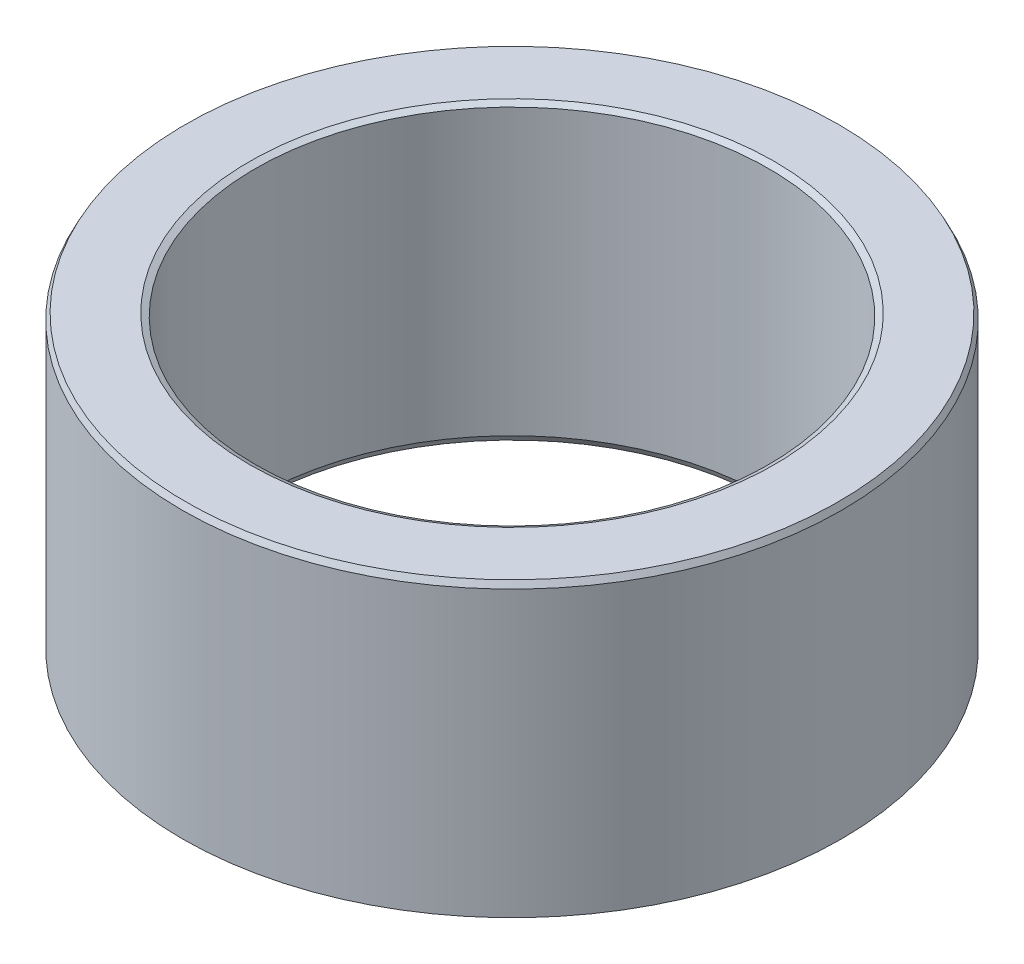
SolidWorks part; units mm, degrees
ref_plane "Front Plane" through (0, 0, 0) normal (0, 0, 1) x (1, 0, 0)
ref_plane "Top Plane" through (0, 0, 0) normal (0, 1, 0) x (1, 0, 0)
ref_plane "Right Plane" through (0, 0, 0) normal (1, 0, 0) x (0, 0, -1)
sketch "Sketch1" plane through (0, 0, 0) normal (0, 1, 0) x (1, 0, 0)
  circle A0 centre (0, 0) radius 30
  dimension "SLEEVE_OD" = 60
extrude "Boss-Extrude1" add sketch "Sketch1" along normal blind 26.7156
sketch "Sketch2" plane through (0, 0, 0) normal (0, 1, 0) x (1, 0, 0)
  circle A0 centre (0, 0) radius 23.344
  dimension "BORE_D" = 46.6879
extrude "Cut-Extrude1" cut sketch "Sketch2" along normal through all
chamfer "Chamfer1" distance 0.5435 angle 27.073 4 edges at (0, 26.7156, 23.344) (0, 0, 23.344) (0, 0, 30) (0, 26.7156, 30) first distance on face at (0, 26.7156, 23.344) first distance on face at (0, 0, 23.344) first distance on face at (0, 26.7156, 30)
